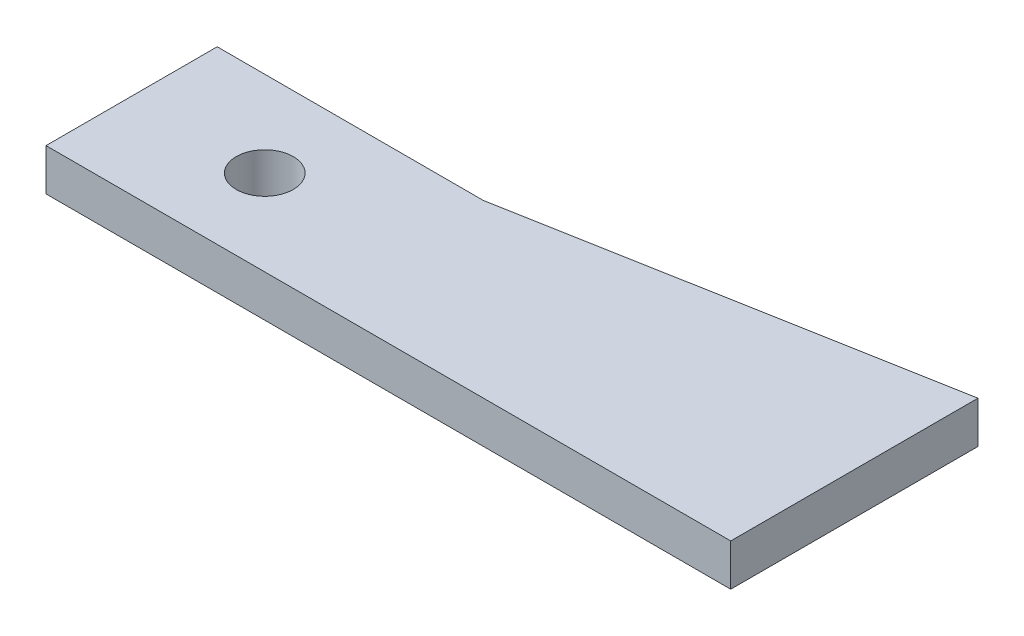
SolidWorks part; units mm, degrees
ref_plane "Front Plane" through (0, 0, 0) normal (0, 0, 1) x (1, 0, 0)
ref_plane "Top Plane" through (0, 0, 0) normal (0, 1, 0) x (1, 0, 0)
ref_plane "Right Plane" through (0, 0, 0) normal (1, 0, 0) x (0, 0, -1)
sketch "Sketch1" plane through (0, 0, 0) normal (0, 1, 0) x (1, 0, 0)
  line L1 (-44.45, -28.575) -> (184.15, -28.575)
  line L2 (-44.45, -28.575) -> (-44.45, 28.575)
  line L3 (-44.45, 28.575) -> (44.45, 28.575)
  line L5 (184.15, 53.975) -> (184.15, -28.575)
  line L7 (184.15, 53.975) -> (44.45, 28.575)
  point P0 (0, 0)
  point P1 (0, 0)
  point P6 (0, 0)
  point P9 (-44.45, 0)
  point P10 (127.5424, 28.575)
  point P11 (0, 28.575)
  dimension "D1" = 228.6
  dimension "D2" = 57.15
  dimension "D3" = 25.4
  dimension "D4" = 139.7
extrude "Boss-Extrude1" add sketch "Sketch1" along normal blind 13.97
sketch "Sketch3" plane through (0, 13.97, 0) normal (0, 1, 0) x (1, 0, 0)
  circle A0 centre (0, 0) radius 9.525
  point P3 (0, 0)
  dimension "D1" = 19.05
extrude "Cut-Extrude1" cut sketch "Sketch3" against normal blind 13.97
